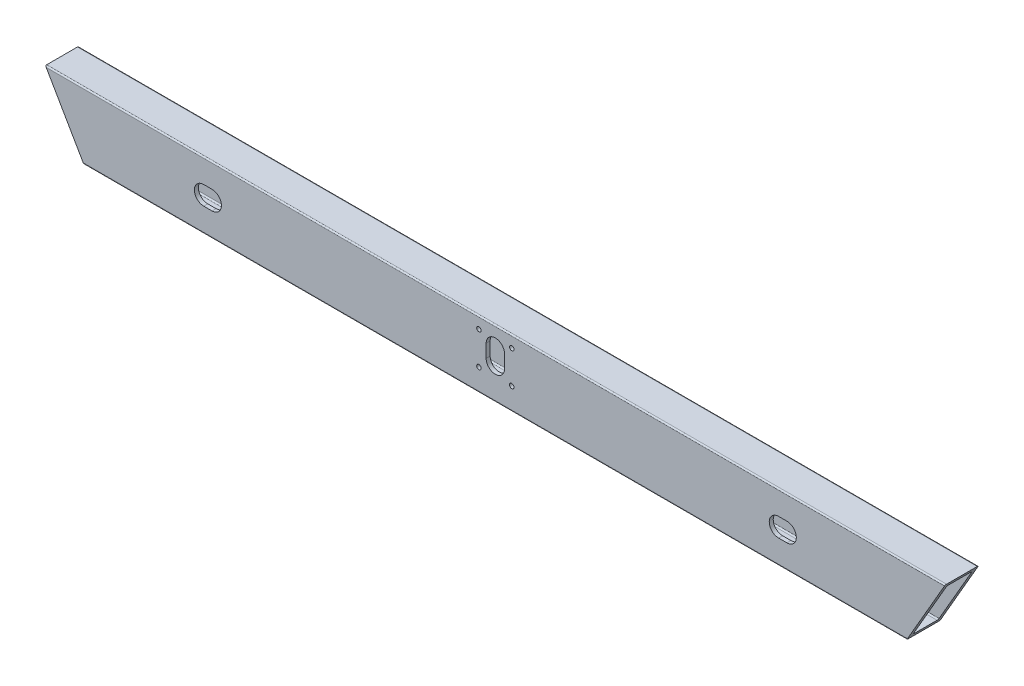
SolidWorks part; units mm, degrees
ref_plane "Front Plane" through (0, 0, 0) normal (0, 0, 1) x (1, 0, 0)
ref_plane "Top Plane" through (0, 0, 0) normal (0, 1, 0) x (1, 0, 0)
ref_plane "Right Plane" through (0, 0, 0) normal (1, 0, 0) x (0, 0, -1)
sketch "Sketch2" plane through (0, 0, 0) normal (0, 0, 1) x (1, 0, 0)
  line L0 (-313.5706, -25.4) -> (-342.9, 25.4)
  line L1 (-342.9, 25.4) -> (342.9, 25.4)
  line L3 (-313.5706, -25.4) -> (313.5706, -25.4)
  line L5 (0, 25.4) -> (0, -25.4) construction
  line L8 (313.5706, -25.4) -> (342.9, 25.4)
  point P0 (0, 0)
  point P4 (0, 0)
  point P8 (0, 25.4)
  dimension "D1" = 50.8
  dimension "D2" = 60
  dimension "D3" = 685.8
extrude "Boss-Extrude1" add sketch "Sketch2" along normal mid plane 25.4 contours L1 L8 L3 L0
sketch "Sketch3" plane through (0, 0, 0) normal (1, 0, 0) x (0, 0, -1)
  line L12 (9.652, -22.352) -> (9.652, 22.352)
  line L13 (-9.652, -22.352) -> (9.652, -22.352)
  line L14 (-9.652, 22.352) -> (-9.652, -22.352)
  line L15 (9.652, 22.352) -> (-9.652, 22.352)
  line L16 (9.652, -22.352) -> (9.652, 22.352)
  line L17 (-9.652, -22.352) -> (9.652, -22.352)
  line L18 (-9.652, 22.352) -> (-9.652, -22.352)
  line L19 (9.652, 22.352) -> (-9.652, 22.352)
  dimension "D1" = 3.048
extrude "Cut-Extrude1" cut sketch "Sketch3" against normal through all and the other way through all contours L16 L19 L18 L17
fillet "Fillet1" radius 1 8 edges at (0, 22.352, 9.652) (0, 22.352, -9.652) (0, -22.352, -9.652) (0, -22.352, 9.652) (0, -25.4, -12.7) (0, -25.4, 12.7) (0, 25.4, -12.7) (0, 25.4, 12.7)
sketch "Sketch4" plane through (0, 0, -12.7) normal (0, 0, -1) x (-1, 0, 0)
  line L1 (7, 0) -> (7, 10)
  line L2 (-7, 0) -> (-7, 10)
  arc A0 (-7, 0) -> (7, 0) centre (0, 0) ccw
  arc A1 (7, 10) -> (-7, 10) centre (0, 10) ccw
  dimension "D1" = 14
  dimension "D2" = 10
extrude "Cut-Extrude2" cut sketch "Sketch4" against normal up to next
sketch "Sketch5" plane through (0, 0, 12.7) normal (0, 0, 1) x (1, 0, 0)
  line L0 (313.5706, -25.4) -> (-313.5706, -25.4) construction
  line L1 (11.7, -6.35) -> (-11.7, -6.35)
  line L2 (12.7, -5.35) -> (12.7, 18.05)
  line L3 (11.7, 19.05) -> (-11.7, 19.05)
  line L4 (-12.7, -5.35) -> (-12.7, 18.05)
  line L5 (12.7, -6.35) -> (-12.7, 19.05) construction
  line L6 (12.7, 19.05) -> (-12.7, -6.35) construction
  line L7 (-342.9, 25.4) -> (342.9, 25.4) construction
  arc A0 (-11.7, -6.35) -> (-12.7, -5.35) centre (-11.7, -5.35) cw
  arc A1 (11.7, -6.35) -> (12.7, -5.35) centre (11.7, -5.35) ccw
  arc A2 (12.7, 18.05) -> (11.7, 19.05) centre (11.7, 18.05) ccw
  arc A3 (-11.7, 19.05) -> (-12.7, 18.05) centre (-11.7, 18.05) ccw
  point P0 (0, 0)
  point P21 (0, 6.35)
  dimension "D2" = 1
  dimension "D1" = 25.4
  dimension "D3" = 6.35
  dimension "D4" = 19.05
  dimension "D5" = 6.35
extrude "Cut-Extrude3" cut sketch "Sketch5" against normal up to next
hole_wizard "M3 Clearance Hole1" positions "Sketch8" profile "Sketch7" hole size "M3" standard "ANSI Metric" end condition up to next
sketch "Sketch8" plane through (0, 0, -9.652) normal (0, 0, 1) x (1, 0, 0)
  line L1 (12.5, 16.5) -> (12.5, -8.5) construction
  line L2 (12.5, -8.5) -> (-12.5, -8.5) construction
  circle A5 centre (-12.5, 16.5) radius 1.25 construction
  point P0 (-12.5, 16.5)
  point P2 (12.5, 16.5)
  point P4 (12.5, -8.5)
  point P6 (-12.5, -8.5)
  point P47 (0, -8.5)
  dimension "D1" = 25
  dimension "D2" = 25
sketch "Sketch7" plane through (-12.5, 16.5, -9.652) normal (1, 0, 0) x (0, -1, 0)
  line L0 (0, 0) -> (0, 3.048)
  line L1 (0, 3.048) -> (1.7, 3.048)
  line L2 (1.7, 3.048) -> (1.7, 0)
  line L5 (1.7, 0) -> (0, 0)
  line L11 (0, -6.35) -> (0, 107.95) construction
  dimension "Thru Hole Dia." = 3.4
  dimension "Thru Hole Depth" = 3.048
sketch "Sketch9" plane through (0, 0, -12.7) normal (0, 0, -1) x (-1, 0, 0)
  line L0 (-222.25, 0) -> (-215.9, 0) construction
  line L1 (-222.25, 7.1437) -> (-215.9, 7.1437)
  line L2 (-222.25, -7.1437) -> (-215.9, -7.1437)
  line L3 (0, 13.97) -> (0, -13.97) construction
  line L4 (222.25, 0) -> (215.9, 0) construction
  line L5 (222.25, 7.1437) -> (215.9, 7.1437)
  line L6 (222.25, -7.1437) -> (215.9, -7.1437)
  arc A0 (-222.25, 7.1437) -> (-222.25, -7.1437) centre (-222.25, 0) ccw
  arc A1 (-215.9, -7.1437) -> (-215.9, 7.1437) centre (-215.9, 0) ccw
  arc A2 (222.25, 7.1437) -> (222.25, -7.1437) centre (222.25, 0) cw
  arc A3 (215.9, -7.1437) -> (215.9, 7.1437) centre (215.9, 0) cw
  point P2 (-219.075, 0)
  point P12 (219.075, 0)
  dimension "D2" = 14.2875
  dimension "D1" = 6.35
  dimension "D3" = 215.9
extrude "Cut-Extrude4" cut sketch "Sketch9" against normal up to next
mirror "Mirror1" about plane through (0, 0, -12.7) normal (0, 0, -1) of bodies 106
sketch "Sketch10" plane through (0, 0, 0) normal (1, 0, 0) x (0, 0, -1)
  line L0 (-12.7, -24.4) -> (-12.7, 24.4) construction
  line L1 (12.7, -25.4) -> (-12.7, -25.4)
  line L2 (12.7, -25.4) -> (12.7, 25.4)
  line L3 (12.7, 25.4) -> (-12.7, 25.4)
  line L4 (-12.7, -25.4) -> (-12.7, 25.4)
  line L5 (12.7, -25.4) -> (-12.7, 25.4) construction
  line L6 (12.7, 25.4) -> (-12.7, -25.4) construction
  line L7 (-11.7, 25.4) -> (11.7, 25.4) construction
  point P0 (0, 0)
extrude "Cut-Extrude5" cut sketch "Sketch10" against normal through all both and the other way through all
